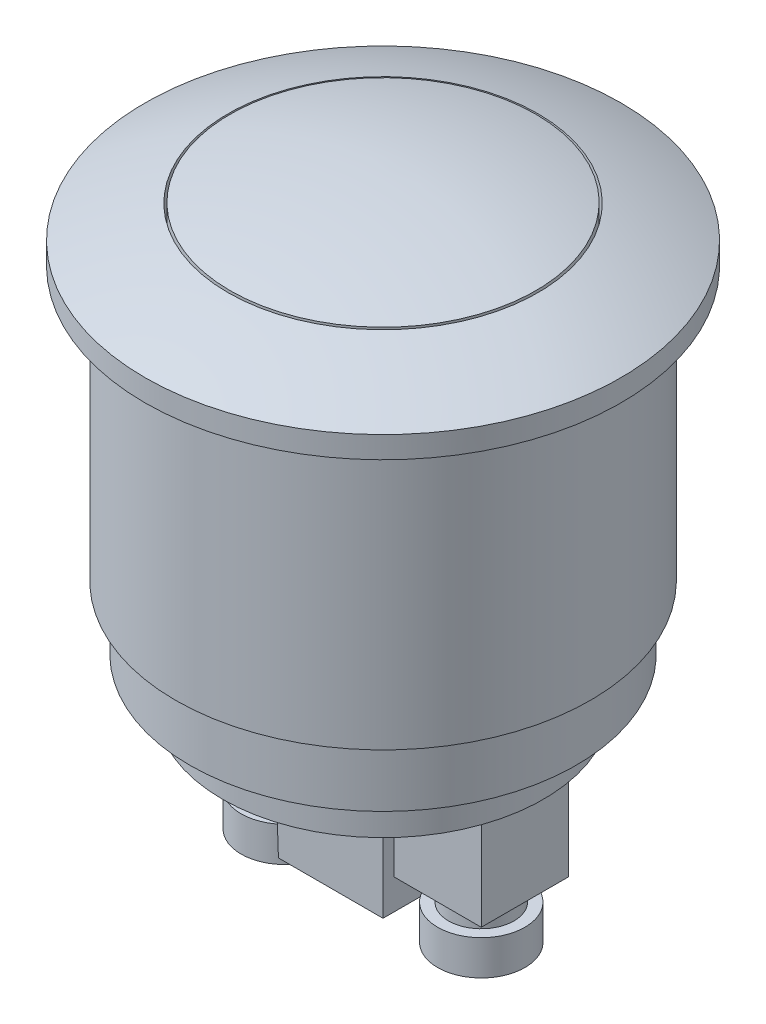
SolidWorks part; units mm, degrees
ref_plane "Спереди" through (0, 0, 0) normal (0, 0, 1) x (1, 0, 0)
ref_plane "Сверху" through (0, 0, 0) normal (0, 1, 0) x (1, 0, 0)
ref_plane "Справа" through (0, 0, 0) normal (1, 0, 0) x (0, 0, -1)
sketch "Эскиз1" plane through (0, 0, 0) normal (0, 1, 0) x (1, 0, 0)
  circle A0 centre (0, 0) radius 10.9
  dimension "D1" = 21.8
extrude "Бобышка-Вытянуть1" add sketch "Эскиз1" along normal blind 1
dome "Купол1" faces to dome 1 distance 2.5 reverse direction no elliptical dome no face at (0, 1, 10.9) parameters "D1"=2.5
sketch "Эскиз2" plane through (0, 0, 0) normal (0, 1, 0) x (1, 0, 0)
  circle A0 centre (0, 0) radius 9.5
  dimension "D1" = 19
extrude "Бобышка-Вытянуть2" add sketch "Эскиз2" against normal blind 12.5
sketch "Эскиз3" plane through (0, 0, 0) normal (0, 1, 0) x (1, 0, 0)
  circle A0 centre (0, 0) radius 8.85
  dimension "D1" = 17.7
extrude "Бобышка-Вытянуть3" add sketch "Эскиз3" against normal blind 15.4
sketch "Эскиз4" plane through (0, 0, 0) normal (0, 1, 0) x (1, 0, 0)
  circle A0 centre (0, 0) radius 7.35
  dimension "D1" = 14.7
extrude "Бобышка-Вытянуть4" add sketch "Эскиз4" against normal blind 17.5
sketch "Эскиз5" plane through (0, 0, 0) normal (0, 1, 0) x (1, 0, 0)
  circle A0 centre (0, 0) radius 7
  circle A1 centre (0, 0) radius 7.1
  dimension "D1" = 14
  dimension "D2" = 0.1
sketch "Эскиз6" plane through (0, 0, 0) normal (0, 1, 0) x (1, 0, 0)
  line L1 (-2.5, -2.5) -> (2.5, -2.5)
  line L2 (-2.5, -2.5) -> (-2.5, 2.5)
  line L3 (-2.5, 2.5) -> (2.5, 2.5)
  line L4 (2.5, -2.5) -> (2.5, 2.5)
  line L5 (-2.5, -2.5) -> (2.5, 2.5) construction
  line L6 (-2.5, 2.5) -> (2.5, -2.5) construction
  point P0 (0, 0)
  dimension "D1" = 5
  dimension "D2" = 5
extrude "Бобышка-Вытянуть5" add sketch "Эскиз6" against normal blind 6 draft 1 from surface starting at face at (0, -17.5, 7.35)
sketch "Эскиз7" plane through (0, 0, 0) normal (0, 1, 0) x (1, 0, 0)
  line L0 (-2.5, -2.5) -> (-2.5, 2.5) construction
  line L1 (-2.5, -2) -> (-6.5, -2)
  line L2 (-2.5, -2) -> (-2.5, 2)
  line L3 (-2.5, 2) -> (-6.5, 2)
  line L4 (-6.5, -2) -> (-6.5, 2)
  line L5 (-6.5, -2) -> (-2.5, 2) construction
  line L6 (-2.5, -2) -> (-6.5, 2) construction
  point P6 (-6.5, 0)
  point P7 (-4.5, 0)
  dimension "D1" = 4
extrude "Бобышка-Вытянуть6" add sketch "Эскиз7" against normal blind 4.5 from surface starting at face at (0, -17.5, 0)
mirror "Зеркальное отражение1" about plane through (0, 0, 0) normal (1, 0, 0) of "Бобышка-Вытянуть6"
sketch "Эскиз8" plane through (0, 0, 0) normal (0, 1, 0) x (1, 0, 0)
  line L0 (-6.5, -2) -> (-2.5, 2) construction
  circle A0 centre (-4.5, 0) radius 1.5
  dimension "D1" = 3
extrude "Бобышка-Вытянуть7" add sketch "Эскиз8" against normal blind 1 from offset 22 offset against normal yes
sketch "Эскиз9" plane through (0, 0, 0) normal (0, 1, 0) x (1, 0, 0)
  circle A0 centre (-4.5, 0) radius 2
  dimension "D1" = 4
extrude "Бобышка-Вытянуть11" add sketch "Эскиз9" against normal blind 1.6 from offset 23 offset against normal yes
mirror "Зеркальное отражение3" about plane through (0, 0, 0) normal (1, 0, 0) of "Бобышка-Вытянуть11", "Бобышка-Вытянуть7"
extrude "Вырез-Вытянуть1" cut sketch "Эскиз5" against normal blind 15 from offset 5
